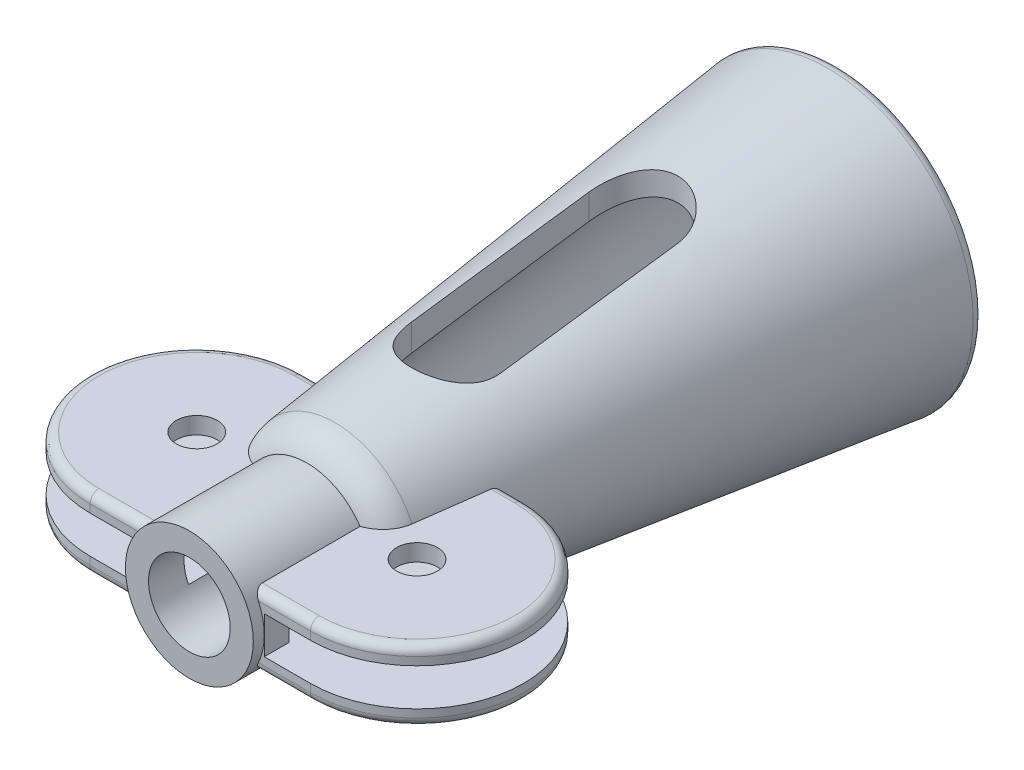
SolidWorks part; units mm, degrees
material "PVC 0.007 Plasticized"
ref_plane "Front Plane" through (0, 0, 0) normal (0, 0, 1) x (1, 0, 0)
ref_plane "Top Plane" through (0, 0, 0) normal (0, 1, 0) x (1, 0, 0)
ref_plane "Right Plane" through (0, 0, 0) normal (1, 0, 0) x (0, 0, -1)
sketch "Sketch1" plane through (0, 0, 0) normal (0, 0, 1) x (1, 0, 0)
  circle A0 centre (0, 0) radius 20.955
  dimension "D1" = 41.91
extrude "Boss-Extrude1" add sketch "Sketch1" along normal blind 76.2 draft 7
shell "Shell4" thickness 3.302 removed face at (20.955, 0, 0) removed face at (11.5988, 0, 76.2)
fillet "Fillet2" radius 5.08 1 edges at (11.5988, 0, 76.2)
sketch3d "3DSketch1"
  line L0 (0, 0, 67.124) -> (0, 0, 87.8708) construction
  circle A0 centre (0, 0, 76.2) radius 8.272 construction
  circle A1 centre (0, 0, 76.2) radius 9.144
  point P2 (0, 0, 84.472)
  point P5 (0, 0, 85.344)
  dimension "D1" = 18.288
extrude "Boss-Extrude2" add sketch "3DSketch1" along direction (0, 0, 1) on the side of the normal mid plane 33.02
shell "Shell5" thickness 3.302 removed face at (9.144, 0, 59.69) removed face at (9.144, 0, 92.71)
sketch "Sketch2" plane through (0, 0, 0) normal (0, 1, 0) x (1, 0, 0)
  line L0 (0, -75.9051) -> (15.748, -75.9051) construction
  line L1 (-9.144, -75.9051) -> (9.144, -75.9051) construction
  line L2 (0, -75.9051) -> (-15.748, -75.9051) construction
  line L3 (-15.748, -75.9051) -> (15.748, -75.9051) construction
  line L4 (-15.748, -60.6651) -> (15.748, -60.6651)
  line L5 (-15.748, -91.1451) -> (15.748, -91.1451)
  arc A0 (-15.748, -60.6651) -> (-15.748, -91.1451) centre (-15.748, -75.9051) ccw
  arc A1 (15.748, -91.1451) -> (15.748, -60.6651) centre (15.748, -75.9051) ccw
  point P4 (0, -75.9051)
  dimension "D1" = 15.748
  dimension "D2" = 15.748
extrude "Boss-Extrude3" add sketch "Sketch2" along normal mid plane 10.16
sketch "Sketch4" plane through (0, 0, 0) normal (0, 1, 0) x (1, 0, 0)
  line L0 (0, -92.71) -> (0, -87.63) construction
  line L1 (-9.144, -92.71) -> (9.144, -92.71) construction
  line L2 (0, -23.0505) -> (0, 23.0505) construction
  line L3 (12.5145, -60.6651) -> (-12.5145, -60.6651) construction
  line L4 (0, -60.6651) -> (0, -63.2051) construction
  line L5 (-9.144, -87.63) -> (9.144, -87.63)
  line L6 (9.144, -87.63) -> (9.144, -92.71)
  line L7 (9.144, -92.71) -> (31.5236, -92.71)
  line L8 (-13.5063, -63.2051) -> (13.5063, -63.2051)
  line L9 (13.5063, -60.6651) -> (13.5063, -63.8903) construction
  line L10 (13.5063, -63.2051) -> (13.5063, -60.6651)
  line L11 (13.5063, -60.6651) -> (31.5236, -60.6651)
  line L12 (31.5236, -60.6651) -> (31.5236, -92.71)
  line L14 (0, -60.6651) -> (0, -95.7491) construction
  line L15 (-13.5063, -63.2051) -> (-13.5063, -60.6651)
  line L16 (-13.5063, -60.6651) -> (-31.5236, -60.6651)
  line L17 (-31.5236, -60.6651) -> (-31.5236, -92.71)
  line L18 (-9.144, -92.71) -> (-31.5236, -92.71)
  line L19 (-9.144, -87.63) -> (-9.144, -92.71)
  dimension "D1" = 5.08
  dimension "D2" = 2.54
  dimension "D3" = 18.288
extrude "Cut-Extrude1" cut sketch "Sketch4" against normal mid plane 5.334 contours L8 L10 L11 L12 L7 L6 L5 L19 L18 L17 L16 L15
sketch "Sketch5" plane through (0, 0, 91.1451) normal (0, 0, 1) x (1, 0, 0)
  circle A0 centre (0, 0) radius 5.842
extrude "Cut-Extrude2" cut sketch "Sketch5" against normal through all
sketch "Sketch6" plane through (0, 0, 0) normal (0, 1, 0) x (1, 0, 0)
  circle A0 centre (15.748, -75.9051) radius 2.921
  circle A1 centre (-15.748, -75.9051) radius 2.921
  dimension "D1" = 5.842
extrude "Cut-Extrude3" cut sketch "Sketch6" against normal mid plane 25.4
sketch "Sketch7" plane through (0, 0, 0) normal (0, 1, 0) x (1, 0, 0)
  line L0 (0, 0) -> (0, -29.21) construction
  line L1 (0, -23.0505) -> (0, 23.0505) construction
  line L2 (0, -29.21) -> (0, -54.61) construction
  line L3 (6.35, -29.21) -> (6.35, -54.61)
  line L4 (-6.35, -29.21) -> (-6.35, -54.61)
  arc A0 (6.35, -29.21) -> (-6.35, -29.21) centre (0, -29.21) ccw
  arc A1 (-6.35, -54.61) -> (6.35, -54.61) centre (0, -54.61) ccw
  point P5 (0, -41.91)
  dimension "D1" = 29.21
extrude "Cut-Extrude4" cut sketch "Sketch7" against normal mid plane 38.1
fillet "Fillet3" radius 1.27 13 edges at (14.1313, 5.08, 60.6651) (11.6755, 5.08, 91.1451) (30.988, 5.08, 75.9051) (14.1313, -5.08, 60.6651) (11.6755, -5.08, 91.1451) (30.988, -5.08, 75.9051) (-14.1313, -5.08, 60.6651) (-11.6755, -5.08, 91.1451) (-30.988, -5.08, 75.9051) (-14.1313, 5.08, 60.6651) (-11.6755, 5.08, 91.1451) (-30.988, 5.08, 75.9051) (20.955, 0, 0)
ref_plane "Plane1" through (0, 0, 7.62) normal (0, 0, 1) x (1, 0, 0)
